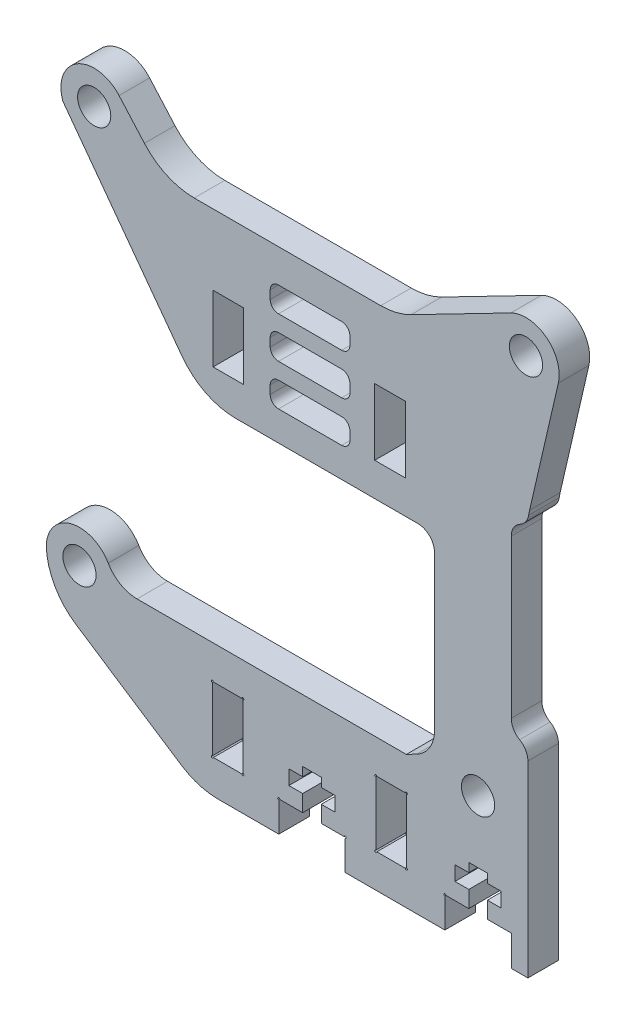
SolidWorks part; units mm, degrees
ref_plane "Front Plane" through (0, 0, 0) normal (0, 0, 1) x (1, 0, 0)
ref_plane "Top Plane" through (0, 0, 0) normal (0, 1, 0) x (1, 0, 0)
ref_plane "Right Plane" through (0, 0, 0) normal (1, 0, 0) x (0, 0, -1)
other "Servo"
sketch "Sketch1" plane through (0, 0, 0) normal (0, 0, 1) x (1, 0, 0)
  line L0 (-63.5, 12.7) -> (0, 12.7) construction
  line L1 (0, 0) -> (-51.5308, 0)
  line L2 (-11.754, 25.4) -> (-63.5, 25.4)
  line L3 (0, 0) -> (1.962, 0)
  line L4 (-80.588, 25.4) -> (-67.888, 25.4) construction
  line L5 (-17.3975, 18.95) -> (-11.9524, 18.95)
  line L6 (-17.596, 18.7516) -> (-17.596, 6.6484)
  line L7 (-17.3975, 6.45) -> (-11.9524, 6.45)
  line L8 (-11.754, 18.7516) -> (-11.754, 6.6484)
  line L9 (-14.9617, 12.7) -> (-20.8037, 12.7) construction
  line L10 (-46.2037, 12.7) -> (-40.3617, 12.7) construction
  line L11 (-43.1944, 18.95) -> (-48.6395, 18.95)
  line L12 (-42.996, 18.7516) -> (-42.996, 6.6484)
  line L13 (-43.1944, 6.45) -> (-48.6395, 6.45)
  line L14 (-48.838, 18.7516) -> (-48.838, 6.6484)
  line L15 (-67.888, 25.4) -> (-67.888, 38.1) construction
  line L16 (-51.5308, 0) -> (-80.588, 19.05)
  line L17 (0, 12.7) -> (-80.588, 12.7) construction
  line L18 (0, 12.7) -> (0, 38.1) construction
  line L19 (0, 38.1) -> (-80.588, 38.1) construction
  line L20 (-80.588, 12.7) -> (-80.588, 38.1) construction
  line L21 (1.962, 25.4) -> (1.962, 0) construction
  line L22 (-80.588, 25.4) -> (-80.588, 19.05)
  line L23 (-74.238, 38.1) -> (-74.238, 12.7) construction
  line L24 (-67.888, 25.4) -> (-63.5, 25.4)
  line L25 (-11.754, 25.4) -> (-0.9777, 31.0285)
  line L26 (1.962, 0) -> (8.312, 0)
  line L27 (8.312, 25.4) -> (8.312, 0)
  arc A0 (-48.6395, 18.95) -> (-48.838, 18.7516) centre (-48.838, 18.95) ccw
  arc A1 (-42.996, 18.7516) -> (-43.1944, 18.95) centre (-42.996, 18.95) ccw
  arc A2 (-43.1944, 6.45) -> (-42.996, 6.6484) centre (-42.996, 6.45) ccw
  arc A3 (-48.838, 6.6484) -> (-48.6395, 6.45) centre (-48.838, 6.45) ccw
  arc A4 (-17.596, 6.6484) -> (-17.3975, 6.45) centre (-17.596, 6.45) ccw
  arc A5 (-11.9524, 6.45) -> (-11.754, 6.6484) centre (-11.754, 6.45) ccw
  arc A6 (-11.754, 18.7516) -> (-11.9524, 18.95) centre (-11.754, 18.95) ccw
  arc A7 (-17.3975, 18.95) -> (-17.596, 18.7516) centre (-17.596, 18.95) ccw
  circle A8 centre (-74.238, 25.4) radius 3.175
  arc A9 (-67.888, 25.4) -> (-80.588, 25.4) centre (-74.238, 25.4) ccw
  circle A10 centre (1.962, 25.4) radius 3.175
  arc A11 (8.312, 25.4) -> (-0.9777, 31.0285) centre (1.962, 25.4) ccw
  circle A13 centre (1.962, 25.4) radius 6.35 construction
  point P55 (8.0345, 27.2565)
  dimension "D8" = 0.3969
  dimension "D9" = 0.3969
  dimension "D10" = 0.3969
  dimension "D11" = 0.3969
  dimension "D12" = 0.3969
  dimension "D13" = 0.3969
  dimension "D14" = 0.3969
  dimension "D15" = 0.3969
  dimension "D19" = 6.35
  dimension "D21" = 3.175
  dimension "D1" = 5.842
  dimension "D2" = 5.842
  dimension "D3" = 12.5
  dimension "D4" = 12.5
  dimension "D5" = 31.242
  dimension "D16" = 19.05
  dimension "D17" = 25.4
  dimension "D18" = 12.7
  dimension "D20" = 76.2
extrude "Boss-Extrude1" add sketch "Sketch1" along normal blind 5.842
fillet "Fillet2" radius 12.7 2 edges at (-51.5308, 0, 2.921) (-80.588, 19.05, 2.921)
fillet "Fillet3" radius 6.35 1 edges at (-67.888, 25.4, 2.921)
sketch "Sketch2" plane through (0, 0, 5.842) normal (0, 0, 1) x (1, 0, 0)
  line L0 (-47.7389, 0) -> (8.312, 0) construction
  line L1 (-23.438, 0) -> (-36.138, 0)
  line L2 (-23.438, 0) -> (-23.438, 5.6436)
  line L3 (-23.6364, 5.842) -> (-28.01, 5.842)
  line L4 (-36.138, 0) -> (-36.138, 5.6436)
  line L5 (-23.438, 0) -> (-36.138, 5.842) construction
  line L6 (-23.438, 5.842) -> (-36.138, 0) construction
  line L7 (8.312, 0) -> (8.312, 25.4) construction
  line L8 (8.1136, 5.842) -> (3.74, 5.842)
  line L9 (8.312, 0) -> (8.312, 5.6436)
  line L10 (-4.388, 0) -> (-4.388, 5.6436)
  line L11 (8.1136, 5.842) -> (8.312, 5.842)
  line L12 (8.312, 5.842) -> (8.312, 5.6436)
  line L13 (-29.788, 2.921) -> (-29.788, 25.4) construction
  line L14 (-11.754, 25.4) -> (-63.2394, 25.4) construction
  line L15 (-31.566, 5.842) -> (-35.9396, 5.842)
  line L16 (-25.3646, 9.017) -> (-28.01, 9.017)
  line L17 (-25.3646, 9.017) -> (-25.3646, 11.7951)
  line L18 (-25.3646, 11.7951) -> (-28.01, 11.7951)
  line L19 (-34.2114, 9.017) -> (-34.2114, 11.7951)
  line L20 (-29.788, 11.7951) -> (-29.788, 9.017) construction
  line L21 (-25.3646, 10.4061) -> (-34.2114, 10.4061) construction
  line L22 (-28.01, 13.4938) -> (-31.566, 13.4938)
  line L23 (-28.01, 13.4938) -> (-28.01, 11.7951)
  line L24 (-31.566, 9.017) -> (-34.2114, 9.017)
  line L25 (-31.566, 13.4938) -> (-31.566, 11.7951)
  line L26 (-29.788, 5.842) -> (-29.788, 13.4938) construction
  line L27 (-28.643, 9.3702) -> (-30.933, 9.3702) construction
  line L28 (-28.01, 9.017) -> (-28.01, 5.842)
  line L29 (-31.566, 9.017) -> (-31.566, 5.842)
  line L30 (-31.566, 11.7951) -> (-34.2114, 11.7951)
  line L31 (3.74, 9.017) -> (3.74, 5.842)
  line L32 (0.184, 9.017) -> (0.184, 5.842)
  line L33 (0.184, 9.017) -> (-2.4614, 9.017)
  line L34 (-2.4614, 9.017) -> (-2.4614, 11.7951)
  line L35 (0.184, 11.7951) -> (-2.4614, 11.7951)
  line L36 (0.184, 13.4938) -> (0.184, 11.7951)
  line L37 (3.74, 13.4938) -> (0.184, 13.4938)
  line L38 (3.74, 13.4938) -> (3.74, 11.7951)
  line L39 (6.3854, 11.7951) -> (3.74, 11.7951)
  line L40 (6.3854, 9.017) -> (6.3854, 11.7951)
  line L41 (6.3854, 9.017) -> (3.74, 9.017)
  line L42 (0.184, 5.842) -> (-4.1896, 5.842)
  arc A0 (-23.438, 5.6436) -> (-23.6364, 5.842) centre (-23.438, 5.842) ccw
  arc A1 (-35.9396, 5.842) -> (-36.138, 5.6436) centre (-36.138, 5.842) ccw
  arc A2 (-4.1896, 5.842) -> (-4.388, 5.6436) centre (-4.388, 5.842) ccw
  arc A4 (8.312, 5.6436) -> (8.1136, 5.842) centre (8.312, 5.842) ccw [skipped]
  point P4 (-29.788, 2.921)
  point P28 (-29.788, 10.4061)
  point P32 (-29.788, 9.3702)
  dimension "D4" = 0.3969
  dimension "D5" = 0.3969
  dimension "D1" = 12.7
  dimension "D2" = 5.842
  dimension "D3" = 31.75
  dimension "D7" = 2.7781
  dimension "D8" = 8.8467
  dimension "D9" = 3.175
  dimension "D10" = 13.4937
  dimension "D11" = 3.556
  dimension "D6" = 2
  dimension "D12" = 2
extrude "Cut-Extrude1" cut sketch "Sketch2" against normal through all
ref_plane "Plane1" through (8.312, 25.4, 5.842) normal (0, 1, 0) x (1, 0, 0)
sketch "Sketch4" plane through (0, 0, 5.842) normal (0, 0, 1) x (1, 0, 0)
  line L0 (-0.9777, 31.0285) -> (-11.754, 25.4) construction
  line L1 (8.312, 5.842) -> (8.312, 25.4) construction
  line L2 (-0.9777, 31.0285) -> (-6.3658, 28.2142)
  line L3 (8.312, 5.842) -> (8.312, 25.4)
  line L4 (-6.3658, 28.2142) -> (-6.3658, 76.2)
  line L5 (8.312, 5.842) -> (8.312, 0)
  line L6 (8.312, 0) -> (11.487, 0)
  line L7 (11.487, 0) -> (11.487, 76.2)
  line L8 (11.487, 76.2) -> (-6.3658, 76.2)
  line L9 (-23.438, 0) -> (-4.388, 0) construction
  arc A0 (8.312, 25.4) -> (-0.9777, 31.0285) centre (1.962, 25.4) ccw construction
  arc A1 (8.312, 25.4) -> (-0.9777, 31.0285) centre (1.962, 25.4) ccw
  dimension "D1" = 3.175
  dimension "D2" = 76.2
extrude "Boss-Extrude2" add sketch "Sketch4" against normal up to surface (5.842 mm away) up to face at (5.137, 25.4, 0)
fillet "Fillet4" radius 6.35 1 edges at (-6.3658, 28.2142, 2.921)
sketch "Sketch5" plane through (0, 0, 5.842) normal (0, 0, 1) x (1, 0, 0)
  line L0 (-6.3658, 64.7261) -> (-50.8158, 64.7261)
  line L1 (-6.3658, 76.2) -> (-6.3658, 32.0616) construction
  line L2 (63.312, 25.4) -> (-46.688, 25.4) construction
  line L3 (-42.8556, 19.0903) -> (-42.8556, 121.6532) construction
  line L4 (-50.8158, 64.7261) -> (-77.4165, 100.7067)
  line L5 (-42.8556, 71.0761) -> (-48.6976, 71.0761)
  line L6 (-42.8556, 71.0761) -> (-42.8556, 83.7761)
  line L7 (-42.8556, 83.7761) -> (-48.6976, 83.7761)
  line L8 (-48.6976, 71.0761) -> (-48.6976, 83.7761)
  line L9 (-45.7766, 77.4261) -> (-11.9524, 77.4261) construction
  line L10 (-42.8556, 71.0761) -> (-48.6976, 83.7761) construction
  line L11 (-42.8556, 83.7761) -> (-48.6976, 71.0761) construction
  line L12 (-11.9524, 18.95) -> (-11.9524, 121.6531) construction
  line L13 (-29.788, 13.4938) -> (-29.788, 64.7261) construction
  line L14 (-6.3658, 64.7261) -> (-6.3658, 76.2)
  line L15 (-6.3658, 76.2) -> (11.487, 76.2)
  line L16 (-71.4306, 102.8261) -> (11.1194, 102.8261) construction
  line L17 (-28.01, 13.4938) -> (-31.566, 13.4938) construction
  line L18 (-17.7944, 71.0761) -> (-17.7944, 83.7761)
  line L19 (-11.9524, 71.0761) -> (-17.7944, 71.0761)
  line L20 (-13.584, 97.2443) -> (-58.034, 97.2443)
  line L21 (-58.034, 97.2443) -> (-66.6699, 107.0282)
  line L22 (-6.3658, 102.7765) -> (-6.3658, 102.8261)
  line L23 (-13.584, 97.2443) -> (8.2116, 108.4712)
  line L24 (11.487, 76.2) -> (17.3065, 101.3971)
  line L25 (-11.9524, 71.0761) -> (-11.9524, 83.7761)
  line L26 (-11.9524, 83.7761) -> (-17.7944, 83.7761)
  line L28 (-11.9524, 71.0761) -> (-17.7944, 83.7761) construction
  line L29 (-11.9524, 83.7761) -> (-17.7944, 71.0761) construction
  arc A0 (-42.996, 18.7516) -> (-43.1944, 18.95) centre (-42.996, 18.95) ccw construction
  arc A1 (-66.6699, 107.0282) -> (-77.4165, 100.7067) centre (-71.4306, 102.8261) ccw
  circle A8 centre (-71.4306, 102.8261) radius 3.175
  circle A9 centre (11.1194, 102.8261) radius 3.175
  arc A11 (-6.3658, 102.7765) -> (-6.3658, 102.8261) centre (-12.7158, 102.8013) ccw
  arc A12 (17.3065, 101.3971) -> (8.2116, 108.4712) centre (11.1194, 102.8261) ccw
  circle A14 centre (11.1194, 102.8261) radius 6.35 construction
  point P6 (-45.7766, 77.4261)
  point P26 (-14.8734, 77.4261)
  point P43 (-52.013, 102.8261)
  point P45 (-12.7158, 102.8013)
  point P47 (-52.013, 102.8261)
  point P48 (-9.6795, 103.7296)
  point P50 (-48.9767, 103.7543)
  point P51 (-30.1556, 102.8261)
  point P52 (-64.2125, 102.8261)
  point P55 (-45.9405, 104.6514)
  point P57 (-6.6433, 104.6578)
  point P58 (-65.4984, 100.1158)
  point P68 (17.0516, 100.1158)
  dimension "D7" = 5.842
  dimension "D8" = 12.7
  dimension "D9" = 28.575
  dimension "D10" = 6.35
  dimension "D16" = 6.35
  dimension "D17" = 3.175
  dimension "D15" = 6.35
  dimension "D4" = 12.7
  dimension "D1" = 39.3261
  dimension "D2" = 12.7
  dimension "D3" = 5.842
  dimension "D5" = 44.45
  dimension "D6" = 82.55
  dimension "D18" = 38.1
extrude "Boss-Extrude3" add sketch "Sketch5" against normal up to surface (5.842 mm away)
fillet "Fillet5" radius 3.175 1 edges at (-6.3658, 64.7261, 2.921)
fillet "Fillet6" radius 12.7 4 edges at (11.487, 76.2, 2.921) (-13.584, 97.2443, 2.921) (-58.034, 97.2443, 2.921) (-50.8158, 64.7261, 2.921)
sketch "Sketch6" plane through (0, 0, 0) normal (0, 0, -1) x (-1, 0, 0)
  line L0 (0, 104.2414) -> (0, 85.2433)
  line L1 (-8.2116, 108.4712) -> (10.8471, 98.6541) construction
  line L2 (0, 85.2433) -> (41.0814, 85.2433)
  line L3 (41.0814, 85.2433) -> (41.0814, 97.2443)
  line L4 (52.3042, 97.2443) -> (16.6627, 97.2443) construction
  line L5 (0, 104.2414) -> (10.8471, 98.6541)
  line L6 (41.0814, 97.2443) -> (16.6627, 97.2443)
  arc A0 (10.8471, 98.6541) -> (16.6627, 97.2443) centre (16.6627, 109.9443) ccw construction
  arc A1 (10.8471, 98.6541) -> (16.6627, 97.2443) centre (16.6627, 109.9443) ccw
extrude "Cut-Extrude2" [suppressed] cut sketch "Sketch6" against normal blind 6.35
sketch "Sketch7" plane through (0, 0, 5.842) normal (0, 0, 1) x (1, 0, 0)
  line L0 (8.312, 71.5775) -> (8.312, 41.415)
  line L1 (11.487, 0) -> (11.487, 74.7525) construction
  line L3 (11.487, 74.7525) -> (11.487, 38.24)
  line L4 (86.8975, 12.7) -> (-82.9735, 12.7) construction
  line L5 (86.8975, 12.7) -> (86.8975, 38.1) construction
  line L6 (86.8975, 38.1) -> (-82.9735, 38.1) construction
  line L7 (-82.9735, 12.7) -> (-82.9735, 38.1) construction
  line L8 (86.8975, 12.7) -> (-82.9735, 38.1) construction
  line L9 (86.8975, 38.1) -> (-82.9735, 12.7) construction
  arc A0 (8.312, 41.415) -> (11.487, 38.24) centre (11.487, 41.415) ccw
  arc A1 (11.487, 74.7525) -> (8.312, 71.5775) centre (11.487, 71.5775) ccw
  point P5 (1.962, 25.4)
  dimension "D1" = 30.1625
  dimension "D2" = 3.175
  dimension "D3" = 25.4
extrude "Cut-Extrude3" cut sketch "Sketch7" against normal through all
fillet "Fillet7" radius 3.175 2 edges at (11.487, 38.24, 2.921) (11.487, 74.7525, 2.921)
sketch "Sketch8" plane through (0, 0, 5.842) normal (0, 0, 1) x (1, 0, 0)
  line L0 (-30.1556, 97.2443) -> (-30.1556, 64.7261) construction
  line L1 (-16.6627, 97.2443) -> (-52.3042, 97.2443) construction
  line L2 (-9.5408, 64.7261) -> (-44.4111, 64.7261) construction
  line L3 (-42.8556, 71.0761) -> (-42.8556, 83.7761) construction
  line L4 (-37.7756, 83.0203) -> (-37.7756, 78.2578)
  line L5 (-22.5356, 90.8943) -> (-37.7756, 90.8943)
  line L6 (-22.5356, 90.8943) -> (-22.5356, 86.1318)
  line L7 (-22.5356, 86.1318) -> (-37.7756, 86.1318)
  line L8 (-37.7756, 90.8943) -> (-37.7756, 86.1318)
  line L9 (-22.5356, 90.8943) -> (-37.7756, 86.1318) construction
  line L10 (-22.5356, 86.1318) -> (-37.7756, 90.8943) construction
  line L11 (-22.5356, 83.0203) -> (-37.7756, 83.0203)
  line L12 (-22.5356, 78.2578) -> (-37.7756, 78.2578)
  line L13 (-22.5356, 83.0203) -> (-22.5356, 78.2578)
  line L14 (-37.7756, 75.1463) -> (-37.7756, 70.3838)
  line L15 (-22.5356, 75.1463) -> (-37.7756, 75.1463)
  line L16 (-22.5356, 70.3838) -> (-37.7756, 70.3838)
  line L17 (-22.5356, 75.1463) -> (-22.5356, 70.3838)
  point P8 (-30.1556, 88.513)
  dimension "D1" = 12.7
  dimension "D2" = 15.24
  dimension "D3" = 4.7625
  dimension "D4" = 6.35
  dimension "D5" = 3
extrude "Cut-Extrude4" cut sketch "Sketch8" against normal through all
fillet "Fillet8" radius 1.5875 12 edges at (-37.7756, 90.8943, 2.921) (-37.7756, 86.1318, 2.921) (-37.7756, 70.3838, 2.921) (-37.7756, 75.1463, 2.921) (-37.7756, 78.2578, 2.921) (-37.7756, 83.0203, 2.921) (-22.5356, 83.0203, 2.921) (-22.5356, 90.8943, 2.921) (-22.5356, 75.1463, 2.921) (-22.5356, 70.3838, 2.921) (-22.5356, 78.2578, 2.921) (-22.5356, 86.1318, 2.921)
